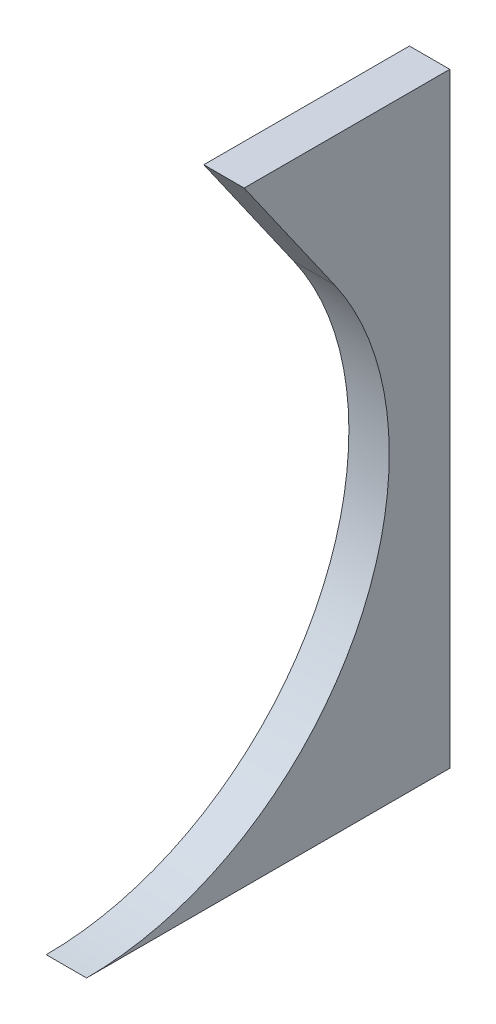
SolidWorks part; units mm, degrees
ref_plane "Front Plane" through (0, 0, 0) normal (0, 0, 1) x (1, 0, 0)
ref_plane "Top Plane" through (0, 0, 0) normal (0, 1, 0) x (1, 0, 0)
ref_plane "Right Plane" through (0, 0, 0) normal (1, 0, 0) x (0, 0, -1)
sketch "Sketch1" plane through (0, 0, 0) normal (1, 0, 0) x (0, 0, -1)
  line L0 (-95.25, 31.75) -> (133.35, 31.75) construction
  line L1 (-95.25, -158.75) -> (133.35, -158.75)
  line L2 (-95.25, -158.75) -> (-95.25, 222.25)
  line L3 (-95.25, 222.25) -> (133.35, 222.25)
  line L4 (133.35, -158.75) -> (133.35, 222.25)
  line L5 (-95.25, -158.75) -> (133.35, 222.25) construction
  line L6 (-95.25, 222.25) -> (133.35, -158.75) construction
  point P0 (0, 0)
  dimension "D1" = 228.6
  dimension "D2" = 381
extrude "Boss-Extrude1" add sketch "Sketch1" along normal blind 25.4
sketch "Sketch2" plane through (25.4, 0, 0) normal (1, 0, 0) x (0, 0, -1)
  line L0 (-95.25, 222.25) -> (-95.25, -158.75) construction
  line L1 (133.35, 222.25) -> (-95.25, 222.25) construction
  circle A0 centre (-95.25, 31.75) radius 190.5
  dimension "D1" = 381
  dimension "D2" = 0
  dimension "D3" = 190.5
extrude "Cut-Extrude1" cut sketch "Sketch2" against normal through all
sketch "Sketch3" plane through (25.4, 0, 0) normal (1, 0, 0) x (0, 0, -1)
  line L1 (60.7985, 141.0163) -> (-14.5807, 248.6689)
  line L2 (60.7985, 141.0163) -> (-203.4462, 141.0163)
  line L5 (-14.5807, 248.6689) -> (-203.4462, 248.6689)
  line L6 (-203.4462, 248.6689) -> (-203.4462, 141.0163)
  arc A0 (-95.25, -158.75) -> (-95.25, 222.25) centre (-95.25, 31.75) ccw construction
  dimension "D1" = 55
extrude "Cut-Extrude2" cut sketch "Sketch3" against normal through all
